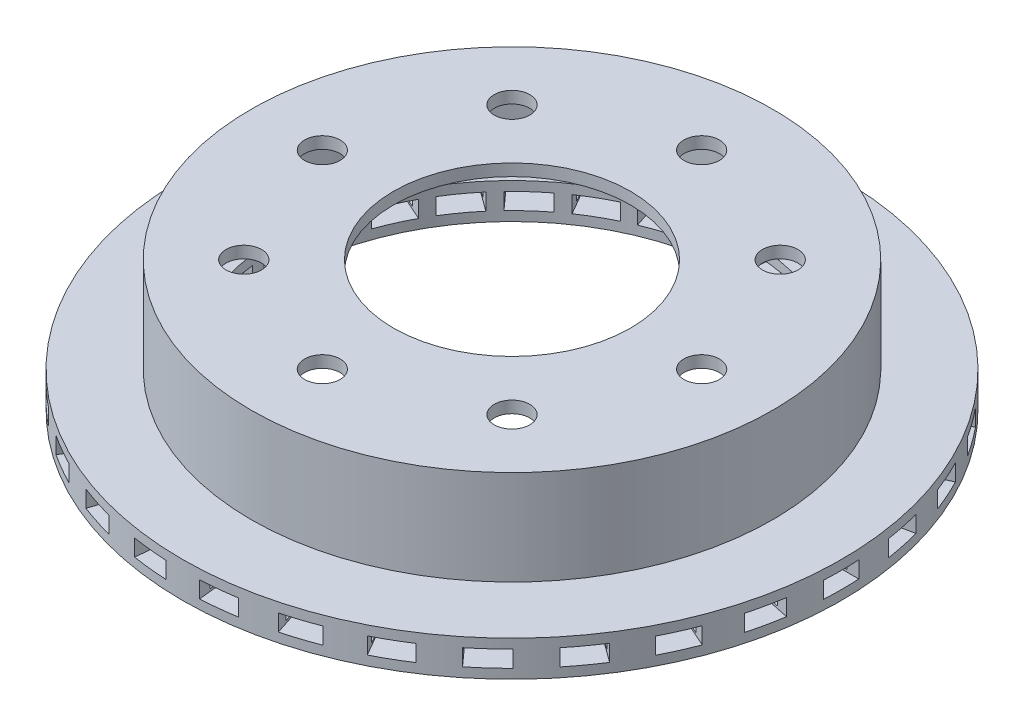
SolidWorks part; units mm, degrees
ref_plane "Front Plane" through (0, 0, 0) normal (0, 0, 1) x (1, 0, 0)
ref_plane "Top Plane" through (0, 0, 0) normal (0, 1, 0) x (1, 0, 0)
ref_plane "Right Plane" through (0, 0, 0) normal (1, 0, 0) x (0, 0, -1)
sketch "Sketch1" plane through (0, 0, 0) normal (0, 1, 0) x (1, 0, 0)
  circle A0 centre (0, 0) radius 139
  dimension "D1" = 278
extrude "Boss-Extrude1" add sketch "Sketch1" along normal mid plane 15
sketch "Sketch2" plane through (0, 7.5, 0) normal (0, 1, 0) x (1, 0, 0)
  circle A0 centre (0, 0) radius 97.5
  dimension "D1" = 195
extrude "Cut-Extrude1" cut sketch "Sketch2" against normal through all both and the other way through all
sketch "Sketch3" plane through (0, 7.5, 0) normal (0, 1, 0) x (1, 0, 0)
  circle A0 centre (0, 0) radius 110
  dimension "D1" = 220
extrude "Boss-Extrude2" add sketch "Sketch3" along normal blind 40
shell "Shell1" thickness 5 removed face at (0, 7.5, 97.5)
sketch "Sketch5" plane through (0, 47.5, 0) normal (0, 1, 0) x (1, 0, 0)
  circle A0 centre (0, 0) radius 50
  dimension "D1" = 100
extrude "Cut-Extrude2" cut sketch "Sketch5" against normal through all
sketch "Sketch6" plane through (0, 47.5, 0) normal (0, 1, 0) x (1, 0, 0)
  line L0 (-110, 0) -> (110, 0) construction
  circle A0 centre (0, 0) radius 110 construction
  circle A1 centre (0, 0) radius 110 construction
sketch "Sketch7" plane through (0, 47.5, 0) normal (0, 1, 0) x (1, 0, 0)
  circle A0 centre (0, 0) radius 80 construction
  circle A1 centre (0, 80) radius 7.5
  dimension "D1" = 160
  dimension "D2" = 15
extrude "Cut-Extrude3" cut sketch "Sketch7" against normal through all both and the other way through all
pattern_circular "CirPattern1" count 8 over 360 about axis through (0, 47.5, 0) along (0, 1, 0) of "Cut-Extrude3"
ref_plane "Plane1" through (139, 0, 0) normal (1, 0, 0) x (0, 0, -1)
sketch "Sketch9" plane through (139, 0, 0) normal (1, 0, 0) x (0, 0, -1)
  line L1 (7.5, 3.5) -> (-7.5, 3.5)
  line L2 (7.5, 3.5) -> (7.5, -3.5)
  line L3 (7.5, -3.5) -> (-7.5, -3.5)
  line L4 (-7.5, 3.5) -> (-7.5, -3.5)
  line L5 (7.5, 3.5) -> (-7.5, -3.5) construction
  line L6 (7.5, -3.5) -> (-7.5, 3.5) construction
  point P0 (0, 0)
  dimension "D1" = 15
  dimension "D2" = 7
extrude "Cut-Extrude4" cut sketch "Sketch9" against normal through all both and the other way through all
pattern_circular "CirPattern2" count 30 over 360 about axis through (0, 7.5, 0) along (0, 1, 0) of "Cut-Extrude4"
